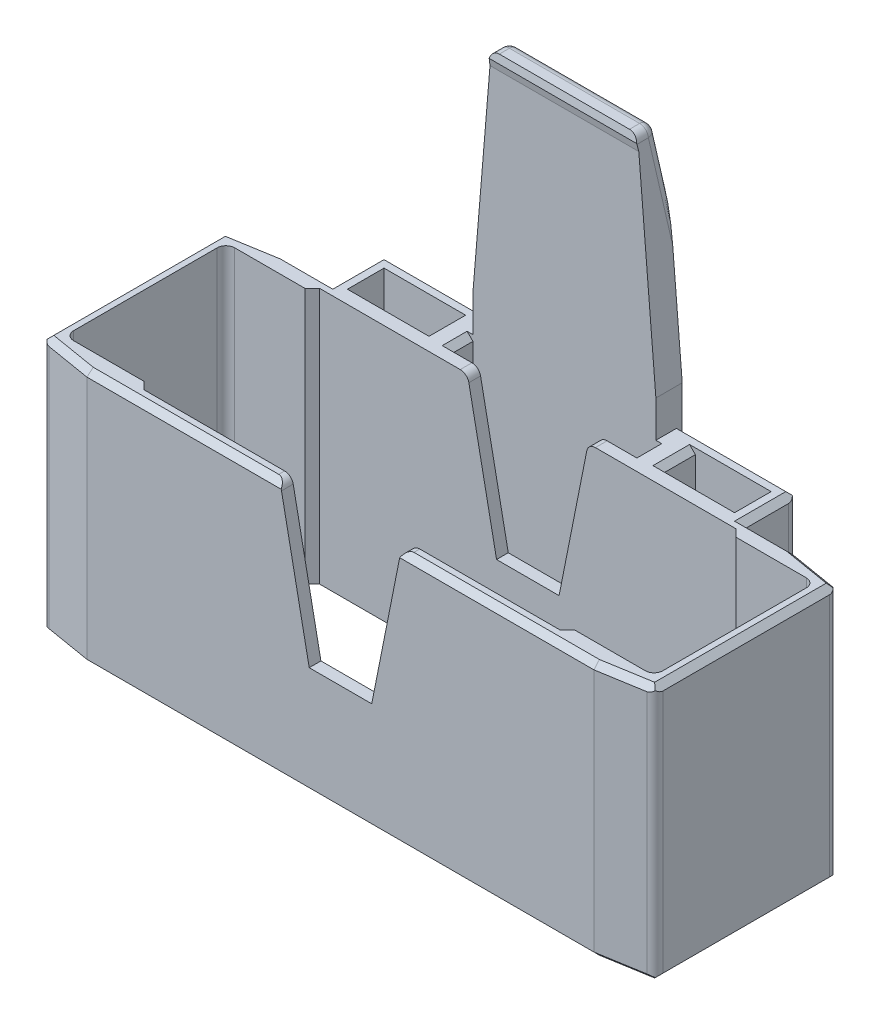
SolidWorks part; units mm, degrees
ref_plane "Front" through (0, 0, 0) normal (0, 0, 1) x (1, 0, 0)
ref_plane "Top" through (0, 0, 0) normal (0, 1, 0) x (1, 0, 0)
ref_plane "Right" through (0, 0, 0) normal (1, 0, 0) x (0, 0, -1)
sketch "Sketch1" plane through (0, 0, 0) normal (0, 1, 0) x (1, 0, 0)
  line L0 (-41.85, 13.6) -> (41.85, 13.6)
  line L1 (-40.25, 12) -> (40.25, 12) construction
  line L2 (-40.25, 12) -> (-40.25, -12) construction
  line L3 (-40.25, -12) -> (40.25, -12) construction
  line L4 (40.25, 12) -> (40.25, -12) construction
  line L5 (41.85, 13.6) -> (41.85, -13.6)
  line L6 (-41.85, -13.6) -> (41.85, -13.6)
  line L7 (-41.85, 13.6) -> (-41.85, -13.6)
  line L8 (0, -1000) -> (0, 49000) construction
  line L9 (-1000, 0) -> (49000, 0) construction
  line L10 (-28.25, 12) -> (-28.25, -49988) construction
  line L11 (28.25, 12) -> (28.25, -49988) construction
  dimension "D1" = 24
  dimension "D2" = 80.5
  dimension "D4" = 12
  dimension "D3" = 1.6
extrude "Boss-Extrude1" add sketch "Sketch1" along normal blind 35
sketch "Sketch2" plane through (0, 0, 0) normal (0, 1, 0) x (1, 0, 0)
  line L0 (0, -1000) -> (0, 49000) construction
  line L1 (-1000, 0) -> (49000, 0) construction
  line L22 (-28.25, 12) -> (-28.25, 11)
  line L23 (-28.25, 11) -> (-40.25, 11)
  line L24 (28.25, 11) -> (40.25, 11)
  line L25 (28.25, 12) -> (28.25, 11)
  line L26 (-40.25, 12) -> (-40.25, -12)
  line L27 (-40.25, -12) -> (40.25, -12)
  line L28 (40.25, -12) -> (40.25, 12)
  line L29 (40.25, 12) -> (-40.25, 12)
  line L30 (-40.25, 11) -> (-40.25, -11)
  line L31 (-28.25, -12) -> (28.25, -12)
  line L32 (40.25, -11) -> (40.25, 11)
  line L33 (28.25, 12) -> (-28.25, 12)
  line L34 (-28.25, -12) -> (-28.25, -11)
  line L35 (-28.25, -11) -> (-40.25, -11)
  line L36 (28.25, -11) -> (40.25, -11)
  line L37 (28.25, -12) -> (28.25, -11)
  dimension "D2" = 12
  dimension "D3" = 22
  dimension "D4" = 80.5
  dimension "D1" = 1.6
extrude "Cut-Extrude1" cut sketch "Sketch2" along normal up to next
sketch "Sketch3" plane through (0, 0, 0) normal (0, 1, 0) x (1, 0, 0)
  line L1 (-28.25, 13.6) -> (28.25, 13.6)
  line L2 (-28.25, 13.6) -> (-28.25, 17)
  line L3 (-28.25, 17) -> (28.25, 17)
  line L4 (28.25, 13.6) -> (28.25, 17)
  line L5 (41.85, 13.6) -> (-41.85, 13.6) construction
  line L8 (0, -1000) -> (0, 49000) construction
  line L9 (-28.25, 12) -> (-28.25, 11) construction
  dimension "D1" = 3.4
extrude "Boss-Extrude2" add sketch "Sketch3" along normal blind 3.2
sketch "Sketch4" plane through (0, 0, 0) normal (0, 1, 0) x (1, 0, 0)
  line L0 (28.25, 17) -> (-28.25, 17) construction
  line L1 (-28.25, 17) -> (28.25, 17)
  line L2 (-28.25, 17) -> (-28.25, 20.6)
  line L3 (-28.25, 20.6) -> (28.25, 20.6)
  line L4 (28.25, 17) -> (28.25, 20.6)
  line L5 (-28.25, 17) -> (-28.25, 13.6) construction
  line L6 (28.25, 13.6) -> (28.25, 17) construction
  dimension "D1" = 3.6
extrude "Boss-Extrude3" add sketch "Sketch4" along normal offset from surface (70 mm away) 35 up to face at (0, 35, 0) offset beyond the face yes
sketch "Sketch5" plane through (0, 0, 0) normal (0, 0, 1) x (1, 0, 0)
  line L0 (0, -928.7342) -> (0, 49071.2658) construction
  line L23 (-12.5, 70) -> (-12.5, 35)
  line L24 (28.25, 70) -> (12.5, 70)
  line L25 (28.25, 70) -> (28.25, 35)
  line L26 (28.25, 35) -> (12.5, 35)
  line L27 (12.5, 70) -> (12.5, 35)
  line L28 (-28.25, 35) -> (-12.5, 35)
  line L29 (-28.25, 70) -> (-28.25, 35)
  line L30 (-28.25, 70) -> (-12.5, 70)
  dimension "D1" = 35
  dimension "D2" = 25
extrude "Cut-Extrude2" cut sketch "Sketch5" against normal up to next from surface starting at face at (0, 36.6, -17)
sketch "Sketch6" plane through (0, 0, 0) normal (0, 1, 0) x (1, 0, 0)
  line L0 (0, -1000) -> (0, 49000) construction
  line L1 (28.25, 17) -> (-28.25, 17) construction
  line L2 (-28.25, 13.6) -> (-12.5, 13.6)
  line L3 (-28.25, 13.6) -> (-28.25, 17)
  line L12 (-28.25, 17) -> (-12.5, 17)
  line L13 (-12.5, 13.6) -> (-12.5, 17)
  line L14 (-12.5, 17) -> (12.5, 17) construction
  line L15 (-12.5, 20.6) -> (-12.5, 17) construction
  line L16 (12.5, 13.6) -> (12.5, 17)
  line L17 (28.25, 17) -> (12.5, 17)
  line L18 (28.25, 13.6) -> (28.25, 17)
  line L19 (28.25, 13.6) -> (12.5, 13.6)
extrude "Boss-Extrude4" add sketch "Sketch6" along normal up to surface (35 mm away) up to face at (20.375, 35, -18.8)
sketch "Sketch7" plane through (0, 0, 0) normal (0, 1, 0) x (1, 0, 0)
  line L4 (12.5, 13.6) -> (12.5, 17)
  line L5 (12.5, 17) -> (-12.5, 17)
  line L6 (-12.5, 17) -> (-12.5, 13.6)
  line L7 (-12.5, 13.6) -> (12.5, 13.6)
  line L8 (12.5, 13.6) -> (12.5, 17)
  line L9 (12.5, 17) -> (-12.5, 17)
  line L10 (-12.5, 17) -> (-12.5, 13.6)
  line L11 (-12.5, 13.6) -> (12.5, 13.6)
  dimension "D1" = 0
extrude "Cut-Extrude3" cut sketch "Sketch7" along normal up to next
sketch "Sketch8" plane through (0, 0, 0) normal (0, 0, 1) x (1, 0, 0)
  line L0 (12.5, 35) -> (28.25, 35) construction
  line L1 (12.5, 40) -> (10, 70)
  line L2 (0, -1000) -> (0, 49000) construction
  line L3 (-12.5, 70) -> (-10, 70)
  line L4 (-12.5, 40) -> (-12.5, 70)
  line L5 (-12.5, 40) -> (-10, 70)
  line L10 (12.5, 35) -> (12.5, 70)
  line L11 (28.25, 35) -> (12.5, 35)
  line L12 (28.25, 0) -> (28.25, 35)
  line L13 (-28.25, 0) -> (28.25, 0)
  line L14 (-28.25, 35) -> (-28.25, 0)
  line L15 (-12.5, 35) -> (-28.25, 35)
  line L16 (-12.5, 70) -> (-12.5, 35)
  line L17 (12.5, 70) -> (-12.5, 70)
  line L18 (12.5, 40) -> (12.5, 70)
  line L25 (12.5, 70) -> (10, 70)
  point P13 (20.375, 35)
  dimension "D2" = 5
  dimension "D3" = 2.5
  dimension "D1" = 0
extrude "Cut-Extrude4" cut sketch "Sketch8" against normal up to next from surface starting at face at (0, 35, -17)
sketch "Sketch9" plane through (0, 0, 0) normal (0, 1, 0) x (1, 0, 0)
  line L6 (0, -1000) -> (0, 49000) construction
  line L61 (-28.25, 20.6) -> (-12.5, 20.6) construction
  line L62 (-26.45, 18.8) -> (-16.1, 18.8)
  line L63 (-26.45, 18.8) -> (-26.45, 13.8)
  line L64 (-26.45, 13.8) -> (-16.1, 13.8)
  line L65 (-16.1, 18.8) -> (-16.1, 13.8)
  line L66 (-12.5, 13.6) -> (-12.5, 17) construction
  line L67 (-28.25, 20.6) -> (-28.25, 13.6) construction
  line L68 (28.25, 12) -> (-28.25, 12) construction
  line L69 (16.1, 18.8) -> (16.1, 13.8)
  line L70 (26.45, 13.8) -> (16.1, 13.8)
  line L71 (26.45, 18.8) -> (26.45, 13.8)
  line L72 (26.45, 18.8) -> (16.1, 18.8)
  dimension "D1" = 1.8
  dimension "D2" = 3.6
  dimension "D3" = 1.8
  dimension "D4" = 1.8
extrude "Cut-Extrude5" cut sketch "Sketch9" along normal up to next
sketch "Sketch10" plane through (0, 0, 0) normal (0, 0, 1) x (1, 0, 0)
  line L0 (0, -1000) -> (0, 49000) construction
  line L1 (-41.85, 0) -> (41.85, 0) construction
  line L2 (-41.85, 35) -> (41.85, 35) construction
  line L3 (-8.25, 35) -> (8.25, 35)
  line L4 (-8.25, 35) -> (-4.2718, 15)
  line L5 (-4.2718, 15) -> (4.2718, 15)
  line L6 (8.25, 35) -> (4.2718, 15)
  line L7 (-12.5, 40) -> (-12.5, 35) construction
  point P5 (0, 0)
  point P9 (0, 0)
  point P12 (0, 15)
  point P13 (0, 35)
  dimension "D1" = 11.25
  dimension "D2" = 15
  dimension "D3" = 4.25
extrude "Cut-Extrude6" cut sketch "Sketch10" against normal up to next and the other way up to next
sketch "Sketch11" plane through (0, 0, 0) normal (0, 1, 0) x (1, 0, 0)
  line L7 (0, -1000) -> (0, 49000) construction
  line L12 (10, 20.6) -> (-10, 20.6) construction
  line L13 (-5, 20.6) -> (5, 20.6)
  line L14 (-5, 20.6) -> (-5, 22.2)
  line L15 (-5, 22.2) -> (5, 22.2)
  line L16 (5, 20.6) -> (5, 22.2)
  dimension "D1" = 1.6
  dimension "D2" = 10
extrude "Boss-Extrude5" add sketch "Sketch11" along normal up to surface (35 mm away) up to face at (-21.275, 35, -16.3)
sketch "Sketch12" plane through (0, 0, 0) normal (0, 0, 1) x (1, 0, 0)
  line L6 (0, -937.4806) -> (0, 49062.5194) construction
  line L12 (-10, 70) -> (-12.5, 40) construction
  line L13 (-10, 70) -> (10, 70) construction
  line L14 (12.5, 40) -> (10, 70) construction
  line L15 (-10, 70) -> (-10.1667, 68)
  line L16 (-10, 70) -> (10, 70)
  line L17 (10.1667, 68) -> (10, 70)
  line L18 (-10.1667, 68) -> (10.1667, 68)
  dimension "D1" = 2
extrude "Boss-Extrude6" add sketch "Sketch12" along normal blind 0.2 from surface starting at face at (0, 36.25, -17)
chamfer "Chamfer1" distance 7.2 distance2 1.2 3 edges at (41.85, 17.5, 13.6) (-41.85, 17.5, -13.6) (0, 70, -20.6) tangent propagation no first distance on face at (0, 21.25, 13.6) first distance on face at (-35.05, 17.5, -13.6) first distance on face at (0, 30.7143, -20.6)
chamfer "Chamfer2" distance 1.2 distance2 7.2 2 edges at (-41.85, 17.5, 13.6) (41.85, 17.5, -13.6) first distance on face at (-41.85, 17.5, 0.6) first distance on face at (41.85, 17.5, -0.6)
chamfer "Chamfer3" distance 1.2 angle 45 6 edges at (28.25, 17.5, -11) (28.25, 17.5, 11) (-28.25, 17.5, 11) (-28.25, 17.5, -11) (-5, 17.5, -22.2) (5, 17.5, -22.2)
chamfer "Chamfer4" distance 0.8 angle 45 37 edges at (-38.25, 35, 13) (-41.85, 35, 0) (-38.25, 35, -13) (31.45, 35, -13.6) (-31.45, 35, -13.6) (38.25, 35, -13) (41.85, 35, 0) (38.25, 35, 13) (-21.45, 35, 13.6) (21.45, 35, 13.6) (-38.25, 0, -13) (-31.45, 0, -13.6) (-28.25, 0, -17.1) (16.625, 0, -20.6) (-16.625, 0, -20.6) (28.25, 0, -17.1) (31.45, 0, -13.6) (38.25, 0, -13) (41.85, 0, 0) (38.25, 0, 13) (0, 0, 13.6) (-38.25, 0, 13) (-41.85, 0, 0) (-12.5, 35, -15.3) (-20.375, 35, -20.6) (12.5, 35, -15.3) (20.375, 35, -20.6) (-12.5, 0, -15.3) (12.5, 0, -15.3) (-28.25, 35, -17.1) (28.25, 35, -17.1) (5, 0, -20.8) (-5, 0, -20.8) (-16.1, 0, -16.3) (16.1, 0, -16.3) (-16.1, 35, -16.3) (16.1, 35, -16.3)
chamfer "Chamfer5" distance 1 distance2 0.2 2 edges at (0, 68, -16.8) (0, 70, -16.8) first distance on face at (0, 69, -16.8)
fillet "Fillet1" radius 1.2 19 edges at (41.85, 17.5, -12.4) (41.85, 17.5, 12.4) (-41.85, 17.5, 12.4) (-41.85, 17.5, -12.4) (-40.25, 17.5, 11) (40.25, 17.5, 11) (40.25, 17.5, -11) (-40.25, 17.5, -11) (28.25, 17.5, -20.6) (-28.25, 17.5, -20.6) (10, 70, -18.2) (-10, 70, -18.2) (8.25, 35, -12.8) (-8.25, 35, -12.8) (8.25, 35, 12.4) (-8.25, 35, 12.4) (10.3, 66.4, -20) (-10.3, 66.4, -20) (0, 70, -19.4)
